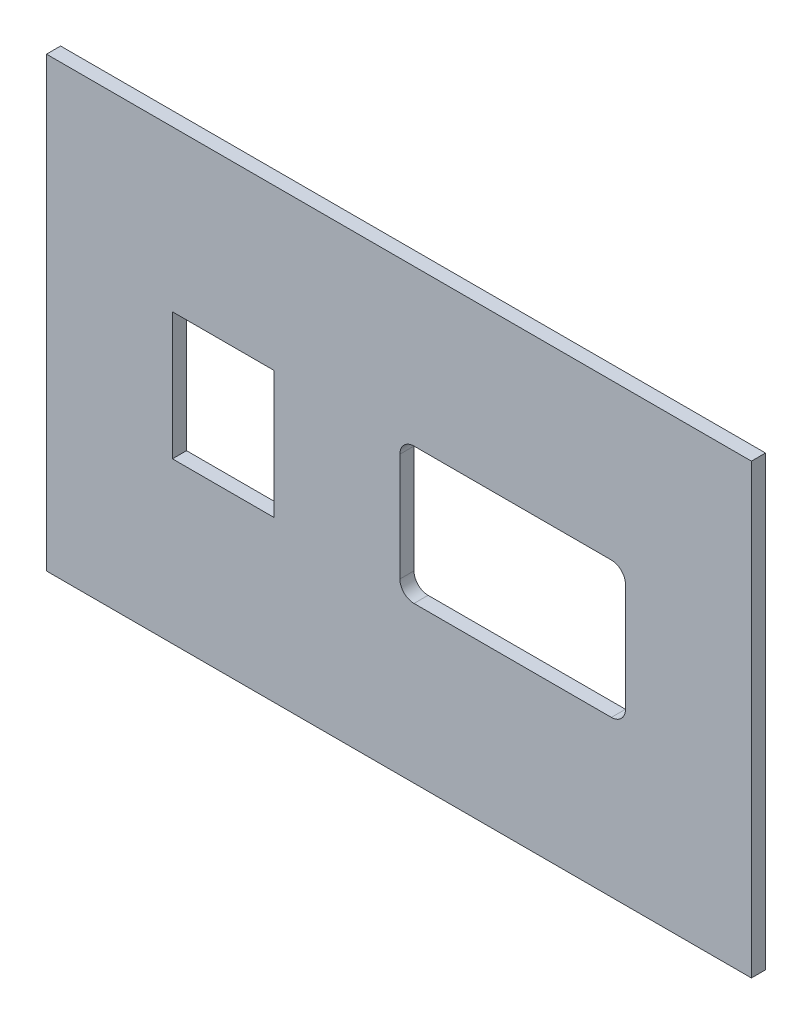
SolidWorks part; units mm, degrees
ref_plane "前基準面" through (0, 0, 0) normal (0, 0, 1) x (1, 0, 0)
ref_plane "上基準面" through (0, 0, 0) normal (0, 1, 0) x (1, 0, 0)
ref_plane "右基準面" through (0, 0, 0) normal (1, 0, 0) x (0, 0, -1)
sketch "草圖1" plane through (0, 0, 0) normal (0, 0, 1) x (1, 0, 0)
  line L1 (-75, 47.625) -> (75, 47.625)
  line L2 (-75, 47.625) -> (-75, -47.625)
  line L3 (-75, -47.625) -> (75, -47.625)
  line L4 (75, 47.625) -> (75, -47.625)
  line L5 (-75, 47.625) -> (75, -47.625) construction
  line L6 (-75, -47.625) -> (75, 47.625) construction
  line L7 (-48.2, 13.55) -> (-26.6, 13.55)
  line L8 (-48.2, 13.55) -> (-48.2, -13.55)
  line L9 (-48.2, -13.55) -> (-26.6, -13.55)
  line L10 (-26.6, 13.55) -> (-26.6, -13.55)
  line L11 (-48.2, 13.55) -> (-26.6, -13.55) construction
  line L12 (-48.2, -13.55) -> (-26.6, 13.55) construction
  line L13 (3.2, 14.5) -> (45.2, 14.5)
  line L14 (0.2, 11.5) -> (0.2, -11.5)
  line L15 (3.2, -14.5) -> (45.2, -14.5)
  line L16 (48.2, 11.5) -> (48.2, -11.5)
  line L17 (0.2, 14.5) -> (48.2, -14.5) construction
  line L18 (0.2, -14.5) -> (48.2, 14.5) construction
  arc A0 (0.2, -11.5) -> (3.2, -14.5) centre (3.2, -11.5) ccw
  arc A1 (45.2, -14.5) -> (48.2, -11.5) centre (45.2, -11.5) ccw
  arc A2 (45.2, 14.5) -> (48.2, 11.5) centre (45.2, 11.5) cw
  arc A3 (3.2, 14.5) -> (0.2, 11.5) centre (3.2, 11.5) ccw
  point P0 (0, 0)
  point P6 (-37.4, 0)
  point P11 (24.2, 0)
  dimension "D9" = 3
  dimension "D1" = 150
  dimension "D2" = 95.25
  dimension "D3" = 27.1
  dimension "D4" = 21.6
  dimension "D5" = 48
  dimension "D6" = 29
  dimension "D7" = 26.8
  dimension "D8" = 26.8
extrude "填料-伸長1" add sketch "草圖1" along normal blind 3 contours L2 L1 L4 L3
extrude "除料-伸長2" cut sketch "草圖1<3>" along normal blind 3 contours L16 L13 L14 L15 | L10 L7 L8 L9 region at (-37.4, 0, 0) region at (24.2, 0, 0)
sketch "草圖1<3>" plane through (0, 0, 0) normal (0, 0, 1) x (1, 0, 0) same geometry as "草圖1"
